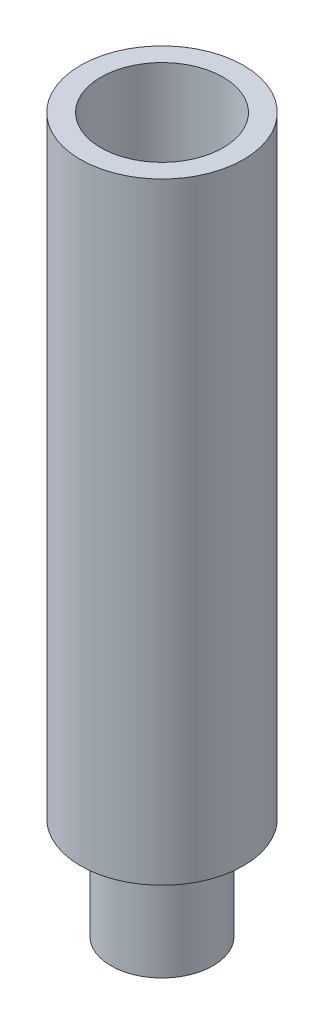
SolidWorks part; units mm, degrees
material "Plain Carbon Steel"
ref_plane "Front Plane" through (0, 0, 0) normal (0, 0, 1) x (1, 0, 0)
ref_plane "Top Plane" through (0, 0, 0) normal (0, 1, 0) x (1, 0, 0)
ref_plane "Right Plane" through (0, 0, 0) normal (1, 0, 0) x (0, 0, -1)
sketch "Sketch1" plane through (0, 0, 0) normal (0, 1, 0) x (1, 0, 0)
  circle A0 centre (0, 0) radius 3
  circle A1 centre (0, 0) radius 2.5
  circle A2 centre (0, 0) radius 4
  dimension "D1" = 5
  dimension "D2" = 6
  dimension "D3" = 8
extrude "Boss-Extrude1" add sketch "Sketch1" along normal blind 5 contours A1 region at (0, 0, 0)
extrude "Boss-Extrude2" add sketch "Sketch1<3>" along normal blind 1 from surface contours A2 starting at face at (0, 5, 2.5)
sketch "Sketch1<3>" plane through (0, 0, 0) normal (0, 1, 0) x (1, 0, 0) same geometry as "Sketch1"
extrude "Boss-Extrude3" add sketch "Sketch1<4>" along normal blind 29 from surface contours A2 A0 region at (-3.8869, 0, 0) starting at face at (0, 6, 4)
sketch "Sketch1<4>" plane through (0, 0, 0) normal (0, 1, 0) x (1, 0, 0) same geometry as "Sketch1"
